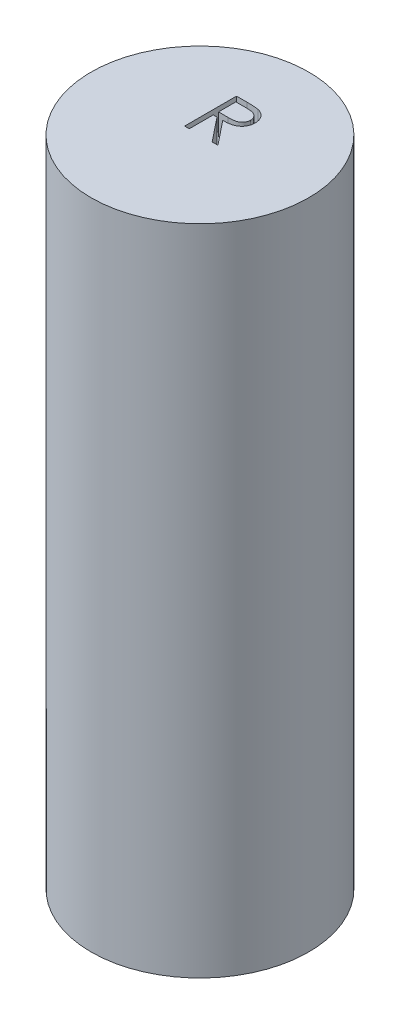
SolidWorks part; units mm, degrees
ref_plane "Front Plane" through (0, 0, 0) normal (0, 0, 1) x (1, 0, 0)
ref_plane "Top Plane" through (0, 0, 0) normal (0, 1, 0) x (1, 0, 0)
ref_plane "Right Plane" through (0, 0, 0) normal (1, 0, 0) x (0, 0, -1)
sketch "Sketch1" plane through (0, 0, 0) normal (0, 1, 0) x (1, 0, 0)
  circle A0 centre (0, 0) radius 10
  dimension "D1" = 20
extrude "Boss-Extrude1" add sketch "Sketch1" along normal blind 4
sketch "Sketch2" plane through (0, 4, 0) normal (0, 1, 0) x (1, 0, 0)
  circle A1 centre (0, 0) radius 1.5
  circle A2 centre (0, 0) radius 8
  circle A3 centre (0, 0) radius 8
  circle A4 centre (0, 0) radius 10 construction
  circle A5 centre (0, 0) radius 10
  circle M2 centre (0, 0) radius 10
  dimension "D2" = 3
  dimension "D1" = 2
extrude "Boss-Extrude2" add sketch "Sketch2" along normal blind 52 contours A1 | A3 M2 region at (0, 4, 0) region at (-9.7172, 4, 0)
sketch "Sketch3" plane through (0, 56, 0) normal (0, 1, 0) x (1, 0, 0)
  circle A0 centre (0, 0) radius 10 construction
  circle A1 centre (0, 0) radius 10
extrude "Boss-Extrude3" add sketch "Sketch3" along normal blind 4
sketch "Sketch4" plane through (0, 60, 0) normal (0, 1, 0) x (1, 0, 0)
  line L0 (-10, 0) -> (10, 0) construction
  circle A0 centre (0, 0) radius 10 construction
  text T0 "R" font "Century Gothic" height in points 18
extrude "Cut-Extrude1" cut sketch "Sketch4" against normal blind 2
